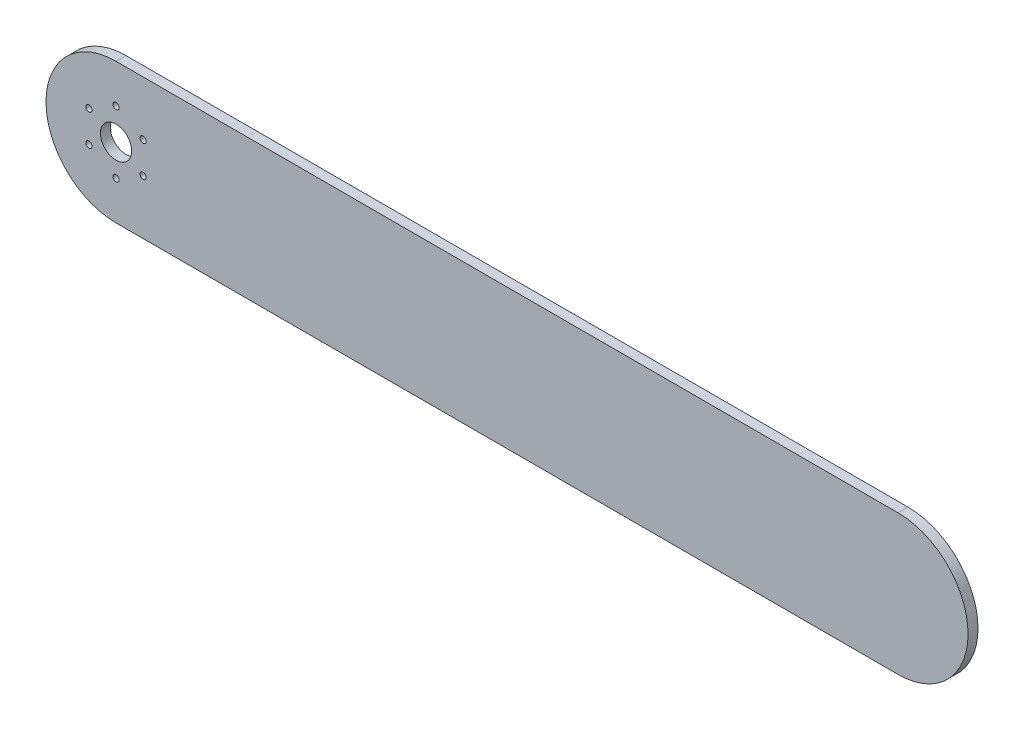
SolidWorks part; units mm, degrees
ref_plane "Front Plane" through (0, 0, 0) normal (0, 0, 1) x (1, 0, 0)
ref_plane "Top Plane" through (0, 0, 0) normal (0, 1, 0) x (1, 0, 0)
ref_plane "Right Plane" through (0, 0, 0) normal (1, 0, 0) x (0, 0, -1)
sketch "Sketch2" plane through (0, 0, 0) normal (0, 0, 1) x (1, 0, 0)
  line L0 (0, 0) -> (500, 0) construction
  line L1 (0, 44.75) -> (500, 44.75)
  line L2 (0, -44.75) -> (500, -44.75)
  arc A0 (0, 44.75) -> (0, -44.75) centre (0, 0) ccw
  arc A1 (500, -44.75) -> (500, 44.75) centre (500, 0) ccw
  circle A2 centre (500, 0) radius 37.25 construction
  circle A3 centre (0, 0) radius 10
  circle A4 centre (0, 20) radius 2
  circle A5 centre (0, 0) radius 20 construction
  circle A6 centre (17.3205, 10) radius 2
  circle A7 centre (17.3205, -10) radius 2
  circle A8 centre (0, -20) radius 2
  circle A9 centre (-17.3205, -10) radius 2
  circle A10 centre (-17.3205, 10) radius 2
  point P3 (250, 0)
  point P27 (0, 0)
  dimension "D2" = 74.5
  dimension "D4" = 20
  dimension "D5" = 4
  dimension "D6" = 40
  dimension "D1" = 500
  dimension "D3" = 7.5
  dimension "D7" = 6
extrude "Boss-Extrude1" add sketch "Sketch2" along normal blind 6.35
equation "\"L1L\"=500"
equation "\"L1Thick\"=6.35"
equation "\"D1@Sketch2\"=\"L1L\""
equation "\"Harm-Drive-Outer\"=74.5"
equation "\"D2@Sketch2\"=\"Harm-Drive-Outer\""
equation "\"D1@Boss-Extrude1\"=\"L1Thick\""
